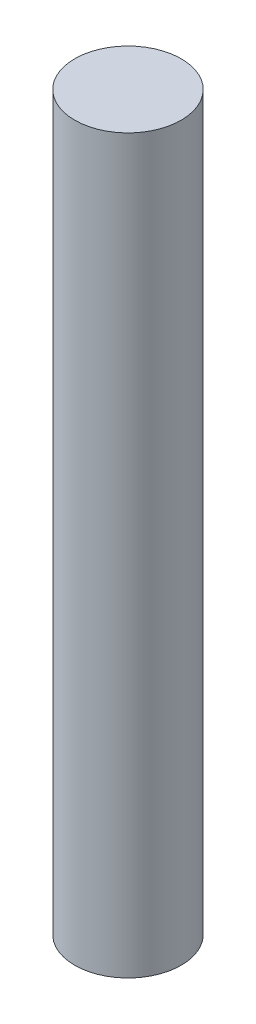
SolidWorks part; units mm, degrees
material "AISI 1020"
ref_plane "Front Plane" through (0, 0, 0) normal (0, 0, 1) x (1, 0, 0)
ref_plane "Top Plane" through (0, 0, 0) normal (0, 1, 0) x (1, 0, 0)
ref_plane "Right Plane" through (0, 0, 0) normal (1, 0, 0) x (0, 0, -1)
sketch "Sketch2" plane through (0, 0, 0) normal (0, 1, 0) x (1, 0, 0)
  circle A0 centre (0, 0) radius 4
  dimension "D1" = 8
extrude "Boss-Extrude1" add sketch "Sketch2" along normal blind 55
